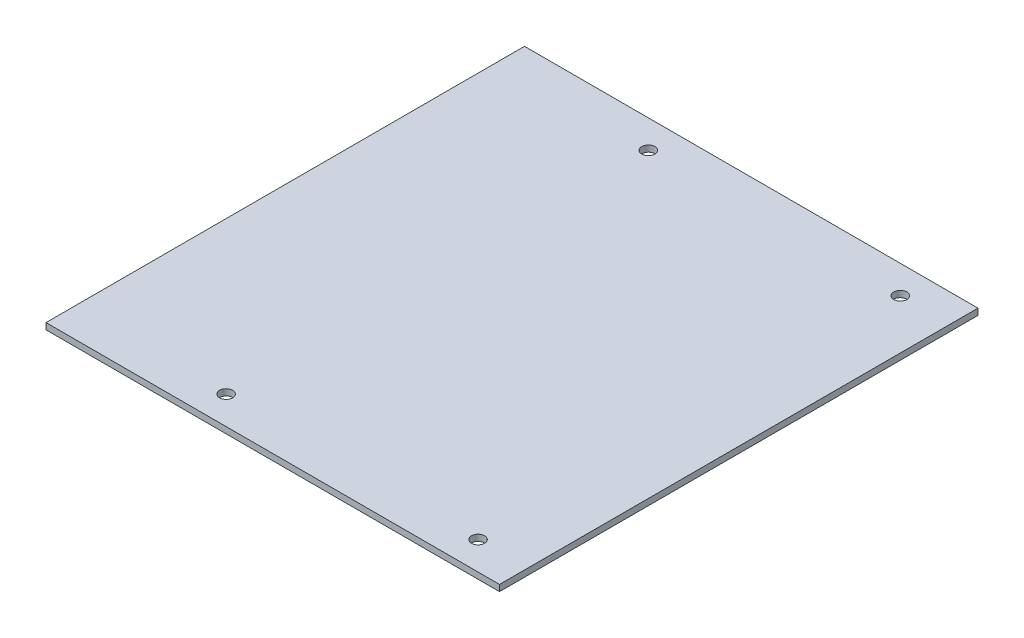
SolidWorks part; units mm, degrees
material "1060 Alloy"
ref_plane "Front Plane" through (0, 0, 0) normal (0, 0, 1) x (1, 0, 0)
ref_plane "Top Plane" through (0, 0, 0) normal (0, 1, 0) x (1, 0, 0)
ref_plane "Right Plane" through (0, 0, 0) normal (1, 0, 0) x (0, 0, -1)
sketch "Sketch1" plane through (0, 0, 0) normal (0, 1, 0) x (1, 0, 0)
  line L0 (361.95, 119.6) -> (-361.95, 119.6) construction
  line L1 (-140.35, -120.6) -> (-368.95, -120.6)
  line L2 (-140.35, -120.6) -> (-140.35, 120.6)
  line L3 (-140.35, 120.6) -> (-368.95, 120.6)
  line L4 (-368.95, -120.6) -> (-368.95, 120.6)
  line L5 (0, -3.8154) -> (0, 119.6) construction
  line L6 (361.3726, 120.6) -> (-361.3726, 120.6) construction
  line L7 (361.3726, -120.6) -> (-361.3726, -120.6) construction
  point P0 (0, 0)
  point P7 (-140.35, 0)
  dimension "D2" = 737.9
  dimension "D3" = 228.6
  dimension "D1" = 241.2
extrude "Boss-Extrude1" add sketch "Sketch1" along normal mid plane 3.175
hole_wizard "M6 Clearance Hole1" positions "Sketch8" profile "Sketch3" hole size "M6" standard "ANSI Metric" end condition through all
sketch "Sketch8" plane through (0, 1.5875, 0) normal (0, 1, 0) x (1, 0, 0)
  line L0 (-165.35, 106.425) -> (-165.35, -106.425) construction
  line L1 (-165.35, -106.425) -> (-292.35, -106.425) construction
  line L3 (-140.35, -120.6) -> (-140.35, 120.6) construction
  point P0 (-292.35, 106.425)
  point P2 (-165.35, 106.425)
  point P4 (-165.35, -106.425)
  point P6 (-292.35, -106.425)
  point P15 (-165.35, 0)
  dimension "D1" = 212.85
  dimension "D2" = 25
  dimension "D3" = 127
sketch "Sketch3" plane through (-292.35, 1.5875, -106.425) normal (1, 0, 0) x (0, 0, 1)
  line L0 (0, 0) -> (0, 3.175)
  line L1 (0, 3.175) -> (3.3, 3.175)
  line L2 (3.3, 3.175) -> (3.3, 0)
  line L5 (3.3, 0) -> (0, 0)
  line L11 (0, -6.35) -> (0, 107.95) construction
  dimension "Thru Hole Dia." = 6.6
  dimension "Thru Hole Depth" = 3.175
sketch "Sketch5" plane through (0, -1.5875, 0) normal (0, -1, 0) x (1, 0, 0)
  line L0 (-175.95, -92.25) -> (-368.95, -92.25)
  line L3 (-368.95, 92.25) -> (-175.95, 92.25)
  line L5 (-368.95, 120.6) -> (-140.35, 120.6) construction
  line L12 (-368.95, -120.6) -> (-368.95, 120.6) construction
  line L16 (-175.95, 92.25) -> (-175.95, -92.25)
  circle A0 centre (-165.35, 106.425) radius 3.3 construction
  circle A1 centre (-165.35, -106.425) radius 3.3 construction
  dimension "D1" = 14.175
  dimension "D2" = 14.175
  dimension "D3" = 14.175
  dimension "D4" = 193
split "Split1" [suppressed] bodies to split 102
sketch "Sketch6" [suppressed] plane through (0, 1.5875, 0) normal (0, 1, 0) x (1, 0, 0)
  line L0 (-140.35, 120.6) -> (-368.95, 120.6) construction
  line L1 (-217.15, -62.5) -> (-292.15, -62.5)
  line L2 (-217.15, -62.5) -> (-217.15, 62.5)
  line L3 (-217.15, 62.5) -> (-292.15, 62.5)
  line L4 (-292.15, -62.5) -> (-292.15, 62.5)
  line L5 (-217.15, -62.5) -> (-292.15, 62.5) construction
  line L6 (-217.15, 62.5) -> (-292.15, -62.5) construction
  point P0 (-254.65, 0)
  point P10 (-254.65, 120.6)
  dimension "D1" = 125
  dimension "D2" = 75
split "Split2" [suppressed] bodies to split 103 104
sketch "Sketch7" plane through (0, 1.5875, 0) normal (0, 1, 0) x (1, 0, 0)
  line L0 (-229.25, -25.4) -> (-229.25, 25.4) construction
  line L1 (-232.425, -25.4) -> (-232.425, 25.4)
  line L2 (-226.075, -25.4) -> (-226.075, 25.4)
  line L5 (-140.35, -120.6) -> (-140.35, 120.6) construction
  arc A0 (-232.425, -25.4) -> (-226.075, -25.4) centre (-229.25, -25.4) ccw
  arc A1 (-226.075, 25.4) -> (-232.425, 25.4) centre (-229.25, 25.4) ccw
  point P2 (-229.25, 0)
  dimension "D1" = 3.175
  dimension "D2" = 50.8
  dimension "D3" = 88.9
extrude "Cut-Extrude1" [suppressed] cut sketch "Sketch7" against normal up to next
equation "\"Length\"= 28.5in"
equation "\"D2@Sketch1\"=\"Length\"+7*2mm"
equation "\"D2@Sketch5\"=\"D1@Sketch5\""
equation "\"D3@Sketch5\"=\"D2@Sketch5\""
